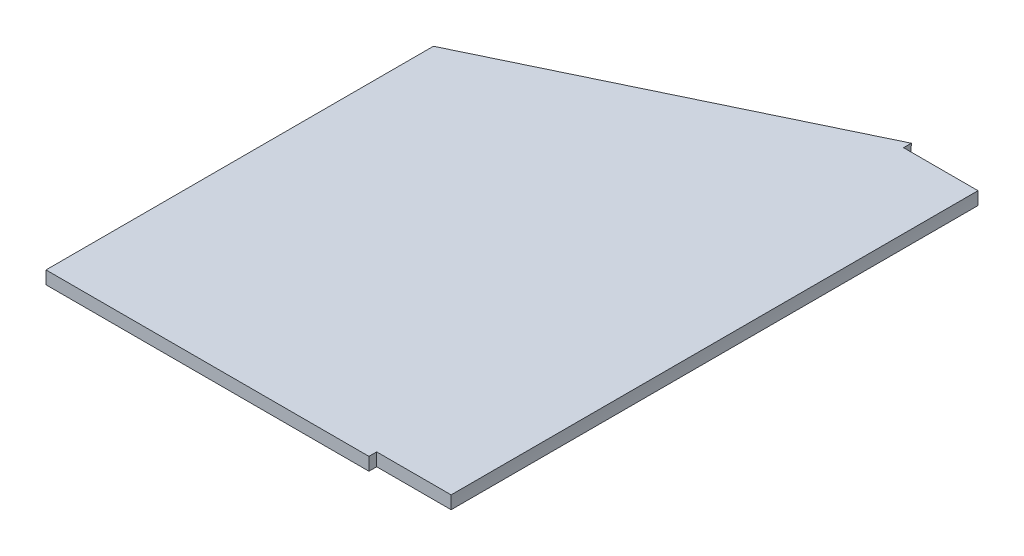
SolidWorks part; units mm, degrees
material "Thornel Mat VMA"
ref_plane "Front Plane" through (0, 0, 0) normal (0, 0, 1) x (1, 0, 0)
ref_plane "Top Plane" through (0, 0, 0) normal (0, 1, 0) x (1, 0, 0)
ref_plane "Right Plane" through (0, 0, 0) normal (1, 0, 0) x (0, 0, -1)
sketch "Sketch1" plane through (0, 0, 0) normal (0, 1, 0) x (1, 0, 0)
  line L0 (-125, 150) -> (-125, 0)
  line L1 (-125, 0) -> (0, 0)
  line L2 (0, 0) -> (0, 210) construction
  line L3 (0, 210) -> (-125, 150)
  line L15 (0, 0) -> (80.75, 0)
  line L17 (0, 210) -> (80.75, 210)
  line L18 (80.75, 0) -> (80.75, 210)
  dimension "D1" = 210
  dimension "D2" = 150
  dimension "D3" = 125
  dimension "D4" = 80.75
extrude "Boss-Extrude1" add sketch "Sketch1" along normal blind 2.5 and the other way blind 2.5
sketch "Sketch2" plane through (0, 0, -210) normal (0, 0, -1) x (-1, 0, 0)
  line L0 (-80.75, -2.5) -> (-80.75, 2.5) construction
  circle A0 centre (-80.75, 0) radius 51.95
  dimension "D1" = 103.9
extrude "Cut-Extrude1" cut sketch "Sketch2" against normal through all
sketch "Sketch3" plane through (0, 0, -210) normal (0, 0, -1) x (-1, 0, 0)
  line L0 (0, 0) -> (-80.75, 0) construction
  circle A0 centre (-80.75, 0) radius 80.75
  dimension "D2" = 161.5
  dimension "D1" = 80.75
extrude "Cut-Extrude2" cut sketch "Sketch3" against normal blind 3
sketch "Sketch4" plane through (0, 0, 0) normal (0, 0, 1) x (1, 0, 0)
  line L0 (0, 0) -> (80.75, 0) construction
  circle A0 centre (80.75, 0) radius 80.75
  dimension "D2" = 161.5
  dimension "D1" = 80.75
extrude "Cut-Extrude3" cut sketch "Sketch4" against normal blind 3
